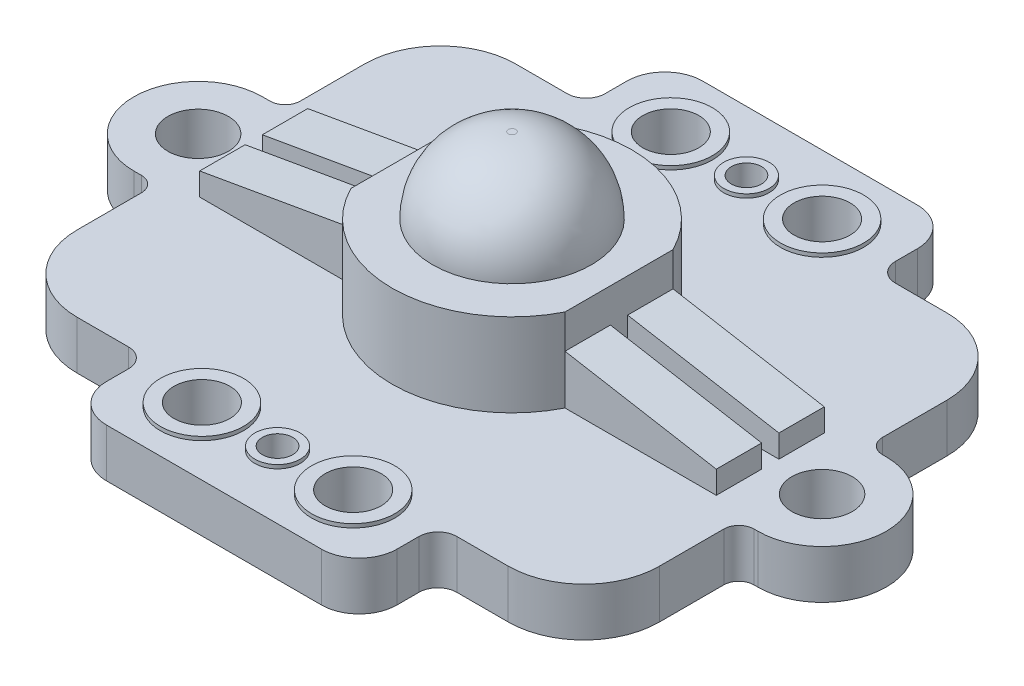
SolidWorks part; units mm, degrees
ref_plane "Front Plane" through (0, 0, 0) normal (0, 0, 1) x (1, 0, 0)
ref_plane "Top Plane" through (0, 0, 0) normal (0, 1, 0) x (1, 0, 0)
ref_plane "Right Plane" through (0, 0, 0) normal (1, 0, 0) x (0, 0, -1)
sketch "Sketch1" plane through (0, 0, 0) normal (0, 1, 0) x (1, 0, 0)
  line L0 (-10.541, 2.159) -> (-10.287, 2.159)
  line L1 (-7.239, 7.366) -> (-5.5118, 7.366)
  line L2 (-9.779, 4.826) -> (-9.779, 2.667)
  line L3 (-7.239, -7.366) -> (-5.5118, -7.366)
  line L4 (9.779, 4.826) -> (9.779, 2.667)
  line L5 (-9.779, 7.366) -> (9.779, -7.366) construction
  line L6 (-9.779, -7.366) -> (9.779, 7.366) construction
  line L7 (-3.6068, 10.0076) -> (3.6068, 10.0076)
  line L8 (-4.8768, 8.7376) -> (-4.8768, 8.001)
  line L9 (-3.6068, -10.0076) -> (3.6068, -10.0076)
  line L10 (4.8768, 8.7376) -> (4.8768, 8.001)
  line L11 (-4.8768, 10.0076) -> (4.8768, -10.0076) construction
  line L12 (-4.8768, -10.0076) -> (4.8768, 10.0076) construction
  line L13 (10.414, -2.159) -> (10.287, -2.159)
  line L16 (5.5118, -7.366) -> (7.239, -7.366)
  line L17 (4.8768, -8.001) -> (4.8768, -8.7376)
  line L18 (-4.8768, -8.001) -> (-4.8768, -8.7376)
  line L19 (-10.287, -2.159) -> (-10.541, -2.159)
  line L20 (10.287, 2.159) -> (10.414, 2.159)
  line L21 (3.3307, 7.366) -> (3.5895, 7.366)
  line L22 (5.5118, 7.366) -> (7.239, 7.366)
  line L23 (9.779, -2.667) -> (9.779, -4.826)
  line L25 (-9.779, -2.667) -> (-9.779, -4.826)
  circle A0 centre (-10.541, 0) radius 1.016
  arc A1 (-10.541, 2.159) -> (-10.541, -2.159) centre (-10.541, 0) ccw
  circle A2 centre (10.414, 0) radius 1.016
  arc A3 (10.414, -2.159) -> (10.414, 2.159) centre (10.414, 0) ccw
  circle A4 centre (0, 7.874) radius 0.508
  circle A5 centre (0, -7.874) radius 0.508
  circle A6 centre (-2.54, 7.874) radius 0.9398
  circle A7 centre (2.54, 7.874) radius 0.9398
  circle A8 centre (-2.54, -7.874) radius 0.9398
  circle A9 centre (2.54, -7.874) radius 0.9398
  arc A10 (-4.8768, 8.001) -> (-5.5118, 7.366) centre (-5.5118, 8.001) cw
  arc A11 (5.5118, 7.366) -> (4.8768, 8.001) centre (5.5118, 8.001) cw
  arc A12 (5.5118, -7.366) -> (4.8768, -8.001) centre (5.5118, -8.001) ccw
  arc A13 (-5.5118, -7.366) -> (-4.8768, -8.001) centre (-5.5118, -8.001) cw
  arc A14 (-9.779, -4.826) -> (-7.239, -7.366) centre (-7.239, -4.826) ccw
  arc A15 (7.239, -7.366) -> (9.779, -4.826) centre (7.239, -4.826) ccw
  arc A16 (7.239, 7.366) -> (9.779, 4.826) centre (7.239, 4.826) cw
  arc A17 (-7.239, 7.366) -> (-9.779, 4.826) centre (-7.239, 4.826) ccw
  arc A18 (-3.6068, 10.0076) -> (-4.8768, 8.7376) centre (-3.6068, 8.7376) ccw
  arc A19 (3.6068, 10.0076) -> (4.8768, 8.7376) centre (3.6068, 8.7376) cw
  arc A20 (3.6068, -10.0076) -> (4.8768, -8.7376) centre (3.6068, -8.7376) ccw
  arc A21 (-4.8768, -8.7376) -> (-3.6068, -10.0076) centre (-3.6068, -8.7376) ccw
  arc A22 (-10.287, -2.159) -> (-9.779, -2.667) centre (-10.287, -2.667) cw
  arc A23 (-10.287, 2.159) -> (-9.779, 2.667) centre (-10.287, 2.667) ccw
  arc A24 (10.287, 2.159) -> (9.779, 2.667) centre (10.287, 2.667) cw
  arc A25 (10.287, -2.159) -> (9.779, -2.667) centre (10.287, -2.667) ccw
  point P0 (0, 0)
  point P6 (0, 0)
  point P34 (0, 0)
  point P35 (0, 0)
  point P36 (0, 0)
  point P37 (0, 0)
  point P50 (4.8768, -7.366)
  point P54 (-4.8768, -7.366)
  point P81 (-9.779, -2.159)
  point P88 (9.779, -2.159)
  dimension "D5" = 2.032
  dimension "D6" = 4.318
  dimension "D9" = 2.032
  dimension "D10" = 4.318
  dimension "D11" = 1.016
  dimension "D12" = 1.016
  dimension "D13" = 1.8796
  dimension "D14" = 1.8796
  dimension "D18" = 1.8796
  dimension "D19" = 1.8796
  dimension "D7" = 0.635
  dimension "D21" = 0.635
  dimension "D22" = 2.54
  dimension "D23" = 1.27
  dimension "D24" = 0.508
  dimension "D1" = 14.732
  dimension "D2" = 19.558
  dimension "D3" = 9.7536
  dimension "D4" = 20.0152
  dimension "D8" = 0.635
  dimension "D15" = 5.08
  dimension "D16" = 2.54
  dimension "D17" = 0.508
  dimension "D20" = 0.508
extrude "Boss-Extrude1" add sketch "Sketch1" along normal mid plane 1.6256 contours L13 A3 L20 L4 L22 L10 L7 L8 L1 L2 L0 A1 L19 L25 L3 L18 L9 L17 L16 L23 A9 A8 A6 A5 A4 A7 A0 A2 region at (-0.0187, 0, 0)
sketch "Sketch2" plane through (0, 0.8128, 0) normal (0, 1, 0) x (1, 0, 0)
  line L2 (-3.5941, 1.8139) -> (-3.5941, -1.8139)
  line L4 (3.5941, 1.8139) -> (3.5941, -1.8139)
  line L5 (-3.5941, 1.8139) -> (3.5941, -1.8139) construction
  line L6 (-3.5941, -1.8139) -> (3.5941, 1.8139) construction
  arc A0 (-3.5941, -1.8139) -> (3.5941, -1.8139) centre (0, 0) ccw
  arc A1 (3.5941, 1.8139) -> (-3.5941, 1.8139) centre (0, 0) ccw
  dimension "D1" = 8.0518
  dimension "D2" = 7.1882
extrude "Boss-Extrude2" add sketch "Sketch2" along normal blind 2.794
sketch "Sketch3" plane through (0, 3.6068, 0) normal (0, 1, 0) x (1, 0, 0)
  circle A0 centre (0, 0) radius 2.667
  dimension "D1" = 5.334
extrude "Boss-Extrude3" add sketch "Sketch3" along normal blind 2.54
fillet "Fillet1" radius 2.54 1 edges at (0, 6.1468, 2.667)
sketch "Sketch4" plane through (0, 0.8128, 0) normal (0, 1, 0) x (1, 0, 0)
  circle A0 centre (2.54, -7.874) radius 1.397
  circle A1 centre (0, -7.874) radius 0.762
  circle A2 centre (-2.54, -7.874) radius 1.397
  circle A3 centre (-2.54, 7.874) radius 1.397
  circle A4 centre (0, 7.874) radius 0.762
  circle A5 centre (2.54, 7.874) radius 1.397
  circle A8 centre (-2.54, 7.874) radius 0.9398 construction
  circle A9 centre (0, 7.874) radius 0.508 construction
  circle A10 centre (2.54, 7.874) radius 0.9398 construction
  circle A11 centre (-2.54, -7.874) radius 0.9398 construction
  circle A12 centre (0, -7.874) radius 0.508 construction
  circle A13 centre (2.54, -7.874) radius 0.9398 construction
  circle A14 centre (-2.54, 7.874) radius 0.9398
  circle A15 centre (0, 7.874) radius 0.508
  circle A16 centre (2.54, 7.874) radius 0.9398
  circle A17 centre (-2.54, -7.874) radius 0.9398
  circle A18 centre (0, -7.874) radius 0.508
  circle A19 centre (2.54, -7.874) radius 0.9398
  dimension "D1" = 2.794
  dimension "D2" = 2.794
  dimension "D3" = 2.794
  dimension "D4" = 2.794
  dimension "D5" = 1.524
  dimension "D6" = 1.524
extrude "Boss-Extrude4" add sketch "Sketch4" against normal offset from surface (1.778 mm away) 0.0254 from offset 0.127 up to face at (-0.0071, -0.8128, 0) offset beyond the face yes
sketch "Sketch5" plane through (0, 0.8128, 0) normal (0, 1, 0) x (1, 0, 0)
  line L0 (0, -3.8418) -> (0, 3.8418) construction
  line L1 (3.5941, -1.8139) -> (8.6741, -1.8139)
  line L2 (3.5941, -1.8139) -> (3.5941, -0.2899)
  line L3 (3.5941, -0.2899) -> (8.6741, -0.2899)
  line L4 (8.6741, -1.8139) -> (8.6741, -0.2899)
  line L5 (3.5941, 1.8139) -> (8.6741, 1.8139)
  line L6 (3.5941, 1.8139) -> (3.5941, 0.2899)
  line L7 (3.5941, 0.2899) -> (8.6741, 0.2899)
  line L8 (8.6741, 1.8139) -> (8.6741, 0.2899)
  line L9 (-8.6741, 1.8139) -> (-8.6741, 0.2899)
  line L10 (-3.5941, 0.2899) -> (-8.6741, 0.2899)
  line L11 (-3.5941, 1.8139) -> (-3.5941, 0.2899)
  line L12 (-3.5941, 1.8139) -> (-8.6741, 1.8139)
  line L13 (-8.6741, -1.8139) -> (-8.6741, -0.2899)
  line L14 (-3.5941, -0.2899) -> (-8.6741, -0.2899)
  line L15 (-3.5941, -1.8139) -> (-3.5941, -0.2899)
  line L16 (-3.5941, -1.8139) -> (-8.6741, -1.8139)
  dimension "D1" = 1.524
  dimension "D2" = 1.524
  dimension "D3" = 5.08
  dimension "D4" = 5.08
extrude "Boss-Extrude5" add sketch "Sketch5" along normal blind 1.651
sketch "Sketch6" plane through (0, 0, 1.8139) normal (0, 0, 1) x (1, 0, 0)
  line L0 (-8.6741, 1.5748) -> (-3.5941, 2.4638)
  line L1 (-8.6741, 2.4638) -> (-8.6741, 0.8128) construction
  line L2 (-3.5941, 2.4638) -> (-8.6741, 2.4638)
  line L3 (-8.6741, 2.4638) -> (-3.5941, 2.4638) construction
  line L4 (-8.6741, 2.4638) -> (-8.6741, 1.5748)
  line L5 (0, -3.8418) -> (0, 3.8418) construction
  line L6 (8.6741, 2.4638) -> (8.6741, 1.5748)
  line L7 (3.5941, 2.4638) -> (8.6741, 2.4638)
  line L8 (8.6741, 1.5748) -> (3.5941, 2.4638)
  dimension "D1" = 0.762
extrude "Cut-Extrude1" cut sketch "Sketch6" against normal up to surface (3.6278 mm away) up to face at (-6.1341, 1.6383, -1.8139)
sketch "Sketch7" plane through (0, -0.8128, 0) normal (0, -1, 0) x (1, 0, 0)
  line L0 (5.7658, 4.699) -> (8.636, 4.699)
  line L1 (5.7658, -1.016) -> (8.636, -1.016)
  line L2 (5.7658, -1.016) -> (5.7658, -2.159)
  line L3 (5.7658, -2.159) -> (8.636, -2.159)
  line L4 (8.636, -1.016) -> (8.636, -2.159)
  line L5 (5.7658, 4.699) -> (5.7658, 3.556)
  line L6 (5.7658, 3.556) -> (8.636, 3.556)
  line L7 (8.636, 4.699) -> (8.636, 3.556)
  line L8 (1.778, 2.794) -> (4.6482, 2.794)
  line L9 (1.778, 2.794) -> (1.778, 1.651)
  line L10 (1.778, 1.651) -> (4.6482, 1.651)
  line L11 (4.6482, 2.794) -> (4.6482, 1.651)
  line L12 (1.778, -2.921) -> (4.6482, -2.921)
  line L13 (1.778, -2.921) -> (1.778, -4.064)
  line L14 (1.778, -4.064) -> (4.6482, -4.064)
  line L15 (4.6482, -2.921) -> (4.6482, -4.064)
  line L19 (4.8768, 8.001) -> (4.8768, 8.7376) construction
  line L20 (-7.747, -3.429) -> (-4.8768, -3.429)
  line L21 (-7.747, -3.429) -> (-7.747, -4.572)
  line L22 (-7.747, -4.572) -> (-4.8768, -4.572)
  line L23 (-4.8768, -3.429) -> (-4.8768, -4.572)
  line L24 (-3.6322, -1.524) -> (-0.762, -1.524)
  line L25 (-3.6322, -1.524) -> (-3.6322, -2.667)
  line L26 (-3.6322, -2.667) -> (-0.762, -2.667)
  line L27 (-0.762, -1.524) -> (-0.762, -2.667)
  line L28 (-4.8768, -8.7376) -> (-4.8768, -8.001) construction
  circle A2 centre (-2.54, -7.874) radius 0.9398 construction
  dimension "D20" = 0.508
  dimension "D1" = 1.143
  dimension "D2" = 2.8702
  dimension "D3" = 1.143
  dimension "D4" = 2.8702
  dimension "D5" = 1.143
  dimension "D6" = 2.8702
  dimension "D7" = 1.143
  dimension "D8" = 2.8702
  dimension "D9" = 0.762
  dimension "D10" = 0.889
  dimension "D11" = 2.54
  dimension "D12" = 6.858
  dimension "D13" = 6.858
  dimension "D14" = 6.858
  dimension "D15" = 1.143
  dimension "D16" = 2.8702
  dimension "D17" = 1.143
  dimension "D18" = 2.8702
  dimension "D19" = 0.508
  dimension "D21" = 1.778
extrude "Boss-Extrude6" add sketch "Sketch7" along normal blind 0.9398
sketch "Sketch8" plane through (0, -0.8128, 0) normal (0, -1, 0) x (-1, 0, 0)
  line L0 (2.54, 7.874) -> (2.54, 5.9795) construction
  line L1 (5.461, -4.064) -> (2.54, -4.064)
  line L2 (5.461, -4.064) -> (5.461, -1.27)
  line L3 (5.461, -1.27) -> (2.54, -1.27)
  line L4 (2.54, -4.064) -> (2.54, -1.27)
  line L5 (5.461, -4.064) -> (2.54, -1.27) construction
  line L6 (5.461, -1.27) -> (2.54, -4.064) construction
  point P0 (4.0005, -2.667)
  dimension "D1" = 2.794
  dimension "D2" = 2.921
extrude "Boss-Extrude7" add sketch "Sketch8" along normal blind 1.143
sketch "Sketch9" plane through (0, -0.8128, 0) normal (0, -1, 0) x (1, 0, 0)
  line L0 (-2.54, 1.27) -> (-2.54, 4.064) construction
  line L1 (-2.159, 2.413) -> (-0.762, 2.413)
  line L2 (-2.159, 2.413) -> (-2.159, 0.508)
  line L3 (-2.159, 0.508) -> (-0.762, 0.508)
  line L4 (-0.762, 2.413) -> (-0.762, 0.508)
  line L5 (-2.159, 2.413) -> (-0.762, 0.508) construction
  line L6 (-2.159, 0.508) -> (-0.762, 2.413) construction
  line L7 (-1.6002, 6.223) -> (0.3048, 6.223)
  line L8 (-1.6002, 6.223) -> (-1.6002, 4.826)
  line L9 (-1.6002, 4.826) -> (0.3048, 4.826)
  line L10 (0.3048, 6.223) -> (0.3048, 4.826)
  line L11 (-1.6002, 6.223) -> (0.3048, 4.826) construction
  line L12 (-1.6002, 4.826) -> (0.3048, 6.223) construction
  line L13 (-1.6002, 9.5971) -> (-1.6002, 7.3837) construction
  line L14 (-2.54, 4.064) -> (-5.461, 4.064) construction
  line L15 (-5.461, 1.27) -> (-2.54, 1.27) construction
  circle A3 centre (-2.54, 7.874) radius 0.9398 construction
  point P0 (-1.4605, 1.4605)
  point P5 (-0.6477, 5.5245)
  point P18 (-1.4605, 1.696)
  dimension "D1" = 1.397
  dimension "D2" = 1.397
  dimension "D3" = 1.905
  dimension "D4" = 1.905
  dimension "D5" = 0.381
  dimension "D6" = 0.762
  dimension "D7" = 0.762
extrude "Boss-Extrude8" add sketch "Sketch9" along normal blind 1.651
equation "\"D8@Sketch1\"=\"D7@Sketch1\""
equation "\"D9@Sketch1\"=\"D5@Sketch1\""
equation "\"D10@Sketch1\"=\"D6@Sketch1\""
equation "\"D12@Sketch1\"=\"D11@Sketch1\""
equation "\"D14@Sketch1\"=\"D13@Sketch1\""
equation "\"D16@Sketch1\"=\"D15@Sketch1\"/2"
equation "\"D18@Sketch1\"=\"D13@Sketch1\""
equation "\"D19@Sketch1\"=\"D13@Sketch1\""
equation "\"D20@Sketch1\"=\"D17@Sketch1\""
equation "\"D2@Sketch4\"=\"D1@Sketch4\""
equation "\"D3@Sketch4\"=\"D1@Sketch4\""
equation "\"D4@Sketch4\"=\"D1@Sketch4\""
equation "\"D2@Sketch5\"=\"D1@Sketch5\""
equation "\"D4@Sketch5\"=\"D3@Sketch5\""
equation "\"D9@Sketch7\"=\"D5@Sketch7\"*2/3"
equation "\"D13@Sketch7\"=\"D12@Sketch7\""
equation "\"D14@Sketch7\"=\"D12@Sketch7\""
equation "\"D20@Sketch7\"=\"D19@Sketch7\""
equation "\"D2@Sketch9\"=\"D1@Sketch9\""
equation "\"D4@Sketch9\"=\"D3@Sketch9\""
